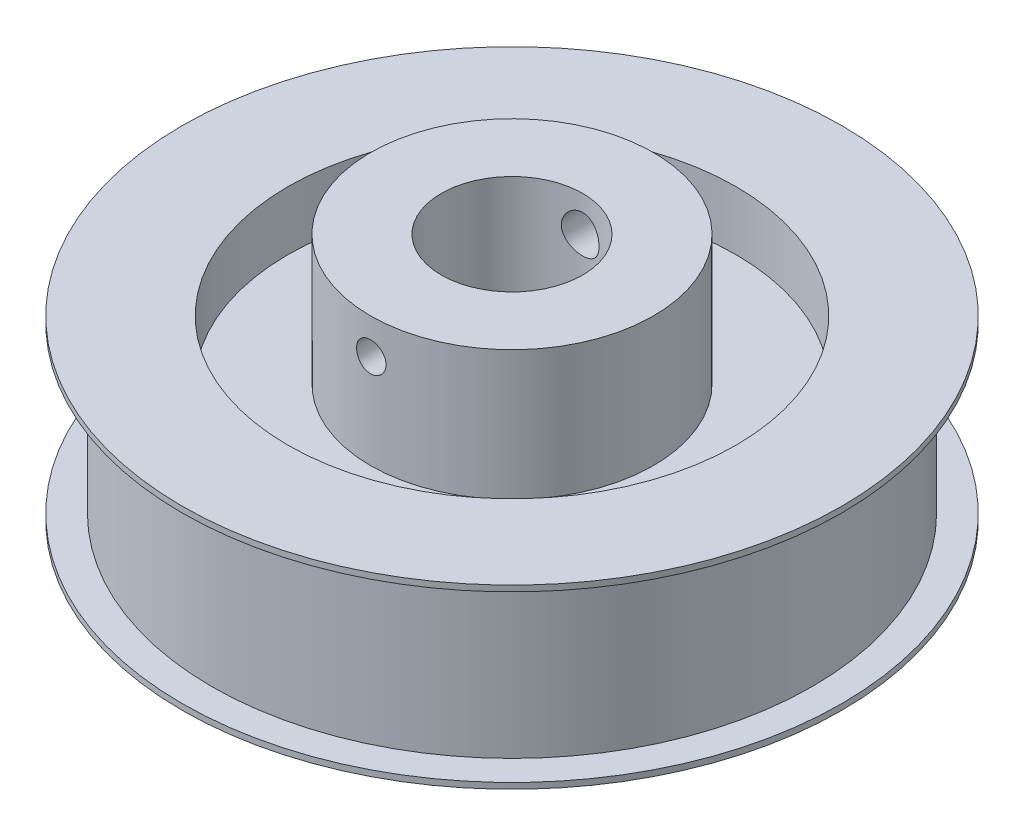
SolidWorks part; units mm, degrees
ref_plane "Alzado" through (0, 0, 0) normal (1, 0, 0) x (0, 1, 0)
ref_plane "Planta" through (0, 0, 0) normal (0, 0, 1) x (0, 1, 0)
ref_plane "Vista lateral" through (0, 0, 0) normal (0, 1, 0) x (-1, 0, 0)
sketch "Croquis1" plane through (0, 0, 0) normal (0, 1, 0) x (-1, 0, 0)
  circle A0 centre (0, 0) radius 25.465
  dimension "D1" = 50.93
extrude "Saliente-Extruir1" add sketch "Croquis1" along normal mid plane 15
sketch "Croquis2" plane through (0, 7.5, 0) normal (0, 1, 0) x (-1, 0, 0)
  circle A3 centre (0, 0) radius 27.965
  dimension "D1" = 55.93
extrude "Saliente-Extruir2" add sketch "Croquis2" against normal blind 0.5
extrude "Saliente-Extruir3" add sketch "Croquis2<2>" along normal blind 0.5 from surface starting at face at (0, -7.5, 25.465)
sketch "Croquis2<2>" plane through (0, 7.5, 0) normal (0, 1, 0) x (-1, 0, 0) same geometry as "Croquis2"
sketch "Croquis3" plane through (0, -7.5, 0) normal (0, 1, 0) x (-1, 0, 0)
  circle A0 centre (0, 0) radius 19
  dimension "D1" = 38
extrude "Saliente-Extruir4" add sketch "Croquis3" along normal blind 21
sketch "Croquis4" plane through (0, -7, 0) normal (0, 1, 0) x (-1, 0, 0)
  circle A0 centre (0, 0) radius 6
  dimension "D1" = 12
extrude "Cortar-Extruir1" cut sketch "Croquis4" against normal through all both and the other way through all
sketch "Croquis5" plane through (0, 13.5, 0) normal (0, 1, 0) x (-1, 0, 0)
  circle A0 centre (0, 0) radius 12
  circle A2 centre (0, 0) radius 19 construction
  circle A3 centre (0, 0) radius 19
  dimension "D1" = 24
extrude "Cortar-Extruir2" cut sketch "Croquis5" against normal offset from surface (11 mm away) 10 up to face at (0, -7.5, 6)
ref_plane "Plano1" through (0, 0, 12) normal (0, 0, 1) x (1, 0, 0)
sketch "Croquis6" plane through (-12, 0, 12) normal (0, 0, -1) x (0, 1, 0)
  line L0 (13.5, 24) -> (7.5, 24) construction
  line L1 (7.5, -15.965) -> (7.5, 39.965) construction
  line L2 (13.5, 24) -> (2.5, 24) construction
  line L3 (10.5, 24) -> (10.5, 0) construction
  line L4 (2.5, 0) -> (13.5, 0) construction
  point P11 (10.5, 12)
hole_wizard "Perforador para roscar para macho de roscar para M31" positions "Croquis6" profile "Croquis7" hole size "M3" standard "DIN" end condition up to next
sketch "Croquis7" plane through (0, 10.5, 12) normal (1, 0, 0) x (0, -1, 0)
  line L0 (0, 0) -> (0, 24)
  line L1 (0, 24) -> (1.25, 24)
  line L2 (1.25, 24) -> (1.25, 0)
  line L5 (1.25, 0) -> (0, 0)
  line L11 (0, -6.35) -> (0, 107.95) construction
  dimension "Diámetro de taladro hasta el siguiente" = 2.5
  dimension "Profundidad de taladro hasta el siguiente" = 24
cosmetic thread "Rosca cosmética2" parameters "D2"=3
ref_plane "Plano2" through (0, 0, 0) normal (0, 0, 1) x (1, 0, 0)
sketch "Croquis8" plane through (0, 0, 0) normal (0, 0, 1) x (1, 0, 0)
  circle A0 centre (0, 10.5) radius 1.25 construction
  circle A1 centre (0, 10.5) radius 1.25
ref_axis "Eje2" through (0, 10.5, -21.2911) along (0, 0, 1)
ref_plane "Plano3" through (0, 0, -12) normal (0, 0, -1) x (-1, 0, 0)
sketch "Croquis9" plane through (0, 0, -12) normal (0, 0, -1) x (-1, 0, 0)
  circle A0 centre (0, 10.5) radius 1.25 construction
  circle A1 centre (0, 10.5) radius 1.25 construction
  point P4 (0, 10.5)
hole_wizard "Taladro de margen para M32" positions "Croquis9" profile "Croquis10" hole size "M3" standard "Ansi Metric" end condition up to next
sketch "Croquis10" plane through (0, 10.5, -12) normal (1, 0, 0) x (0, 1, 0)
  line L0 (0, 0) -> (0, 6)
  line L1 (0, 6) -> (1.6, 6)
  line L2 (1.6, 6) -> (1.6, 0)
  line L5 (1.6, 0) -> (0, 0)
  line L11 (0, -6.35) -> (0, 107.95) construction
  dimension "Diámetro de taladro hasta el siguiente" = 3.2
  dimension "Profundidad de taladro hasta el siguiente" = 6
equation "\"Dp\"= 50.93"
equation "\"D1@Croquis1\"=\"Dp\""
equation "\"Dm\"= 38"
equation "\"De\"= \"Dp\" + 5"
equation "\"F\"= 15"
equation "\"L\"= 21"
equation "\"D1@Croquis2\"=\"De\""
equation "\"D1@Saliente-Extruir1\"=\"F\""
equation "\"D1@Saliente-Extruir4\"=\"L\""
equation "\"deje\"=12"
equation "\"D1@Croquis4\"=\"deje\""
equation "\"D1@Croquis3\"=\"Dm\""
